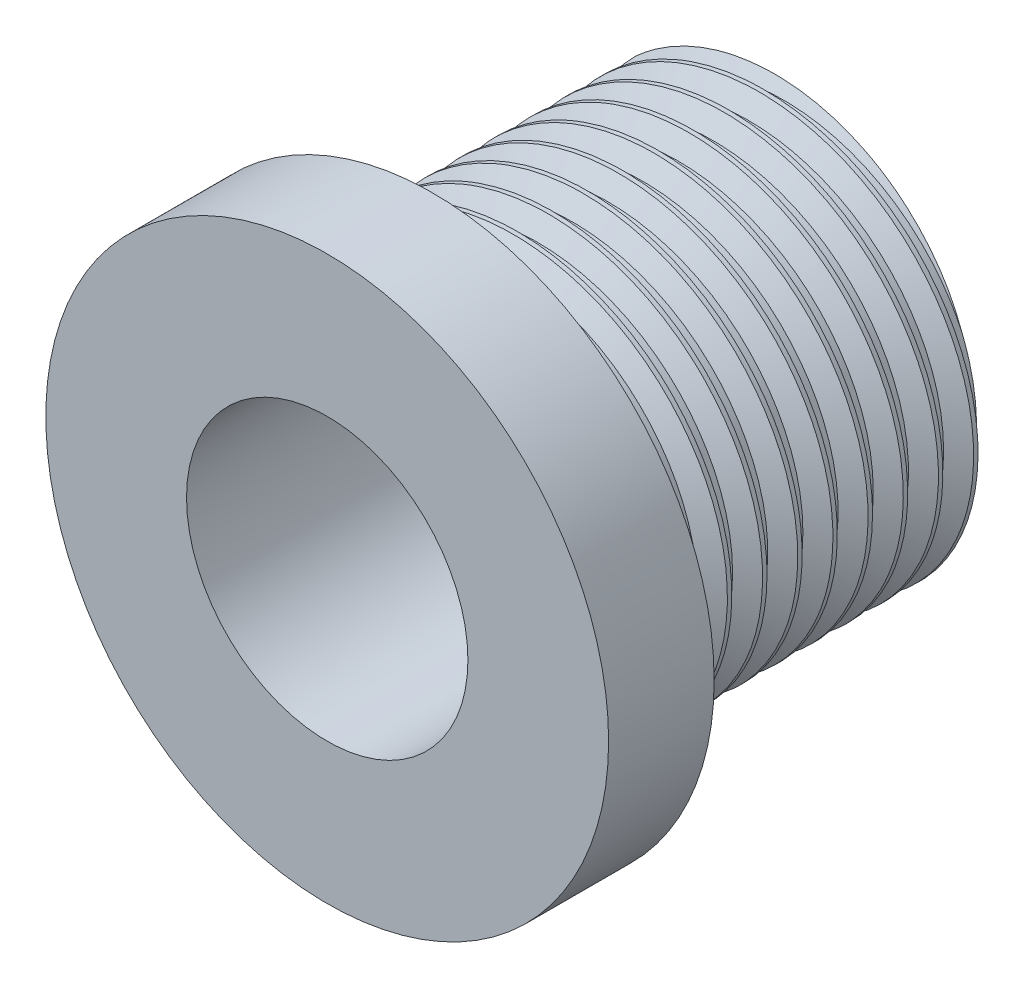
SolidWorks part; units mm, degrees
ref_plane "Front Plane" through (0, 0, 0) normal (0, 0, 1) x (1, 0, 0)
ref_plane "Top Plane" through (0, 0, 0) normal (0, 1, 0) x (1, 0, 0)
ref_plane "Right Plane" through (0, 0, 0) normal (1, 0, 0) x (0, 0, -1)
sketch "Sketch1" plane through (0, 0, 0) normal (0, 0, 1) x (1, 0, 0)
  circle A0 centre (0, 0) radius 6
extrude "Boss-Extrude1" add sketch "Sketch1" along normal blind 10 contours A0
sketch "Sketch2" plane through (0, 0, 10) normal (0, 0, 1) x (1, 0, 0)
  circle A0 centre (0, 0) radius 4
extrude "Cut-Extrude1" cut sketch "Sketch2" against normal through all both and the other way through all
thread "Thread1" pitch 1 method cut profile "Thread Profile1" start angle 0, offset 0, length 10, pitch 1, diameter 12
ref_plane "Plane1" through (-6, 0, 10) normal (0, -1, 0) x (-1, 0, 0)
sketch "Thread Profile1" plane through (-6, 0, 10) normal (0, -1, 0) x (-1, 0, 0)
  line L0 (0, 0) -> (0, 1) construction
  line L11 (0, 0) -> (0, 0.875)
  line L12 (0, 0.875) -> (-0.5413, 0.5625)
  line L13 (-0.5413, 0.5625) -> (-0.5413, 0.3125)
  line L15 (-0.5413, 0.3125) -> (0, 0)
  line L17 (-0.5413, 0.4375) -> (0, 0.4375) construction
  point P2 (0, 0)
  dimension "Pitch" = 1
  dimension "Profile_Angle" = 60
  dimension "Profile_Land" = 0.25
  dimension "Profile_Height" = 0.5413
sketch "Sketch10" plane through (0, 0, 10) normal (0, 0, 1) x (1, 0, 0)
  circle A0 centre (0, 0) radius 8
extrude "Boss-Extrude2" add sketch "Sketch10" along normal blind 3
extrude "Cut-Extrude2" cut sketch "Sketch2<2>" along normal blind 35
sketch "Sketch2<2>" plane through (0, 0, 10) normal (0, 0, 1) x (1, 0, 0) same geometry as "Sketch2"
